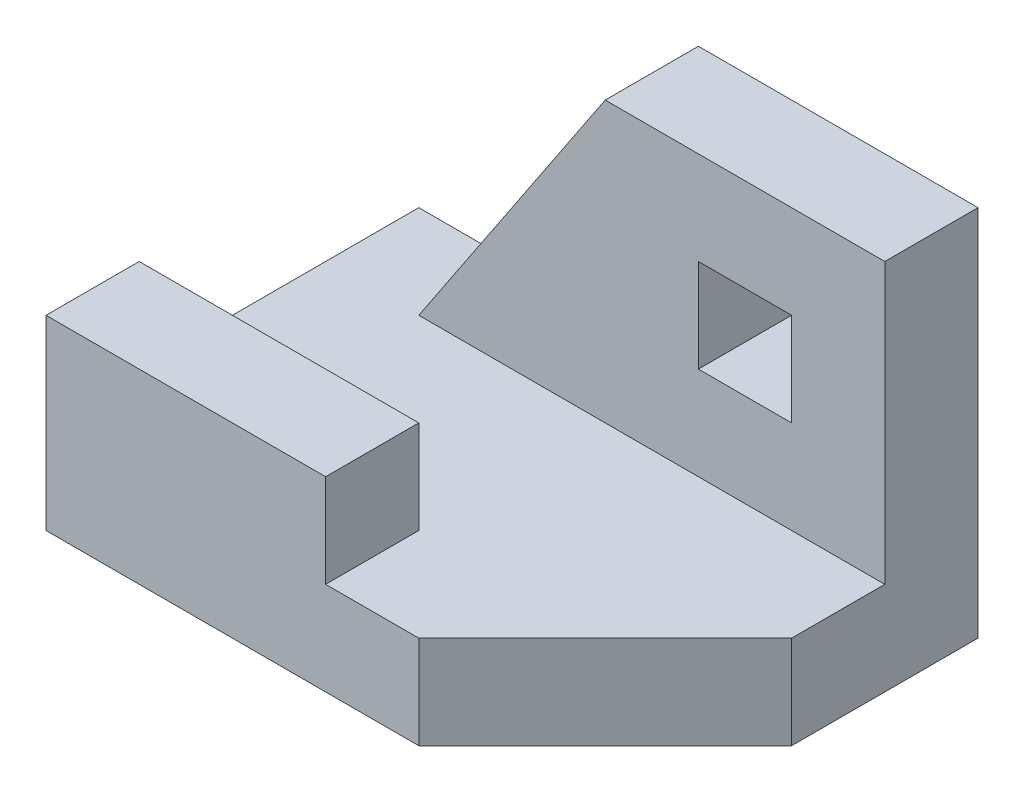
SolidWorks part; units mm, degrees
ref_plane "前基準面" through (0, 0, 0) normal (0, 0, 1) x (1, 0, 0)
ref_plane "上基準面" through (0, 0, 0) normal (0, 1, 0) x (1, 0, 0)
ref_plane "右基準面" through (0, 0, 0) normal (1, 0, 0) x (0, 0, -1)
sketch "草圖1" plane through (0, 0, 0) normal (0, 1, 0) x (1, 0, 0)
  line L0 (4, 0) -> (6, 2)
  line L1 (0, 0) -> (4, 0)
  line L2 (0, 0) -> (0, 4)
  line L3 (0, 4) -> (6, 4)
  line L4 (6, 2) -> (6, 4)
  line L5 (0, 1) -> (3, 1)
  line L6 (3, 1) -> (3, 0)
  line L7 (1, 4) -> (1, 3)
  line L8 (1, 3) -> (6, 3)
  dimension "D1" = 6
  dimension "D2" = 4
  dimension "D3" = 2
  dimension "D4" = 4
  dimension "D5" = 3
  dimension "D6" = 1
  dimension "D7" = 1
  dimension "D8" = 1
extrude "填料-伸長1" add sketch "草圖1" along normal blind 1 contours L7 L8 L4 L3 | L8 L7 L3 L2 L5 L6 L1 L0 L4 | L6 L5 L2 L1 region at (2.8095, 0, -1.9762) region at (1.5, 0, -0.5) region at (3.5, 0, -3.5)
extrude "填料-伸長2" add sketch "草圖1<3>" along normal blind 2 contours L6 L5 L2 L1 region at (1.5, 0, -0.5)
sketch "草圖1<3>" plane through (0, 0, 0) normal (0, 1, 0) x (1, 0, 0) same geometry as "草圖1"
extrude "填料-伸長3" add sketch "草圖1<4>" along normal blind 4 contours L7 L8 L4 L3 region at (3.5, 0, -3.5)
sketch "草圖1<4>" plane through (0, 0, 0) normal (0, 1, 0) x (1, 0, 0) same geometry as "草圖1"
sketch "草圖2" plane through (0, 0, -3) normal (0, 0, 1) x (1, 0, 0)
  line L0 (1, 4) -> (6, 4) construction
  line L1 (4, 2) -> (5, 2)
  line L2 (4, 2) -> (4, 3)
  line L3 (4, 3) -> (5, 3)
  line L4 (5, 2) -> (5, 3)
  line L5 (4, 2) -> (5, 3) construction
  line L6 (4, 3) -> (5, 2) construction
  line L7 (6, 4) -> (6, 1) construction
  line L8 (1, 4) -> (3, 4)
  line L9 (3, 4) -> (1, 1)
  line L10 (1, 1) -> (1, 4)
  point P0 (4.5, 2.5)
  dimension "D1" = 1
  dimension "D2" = 1
  dimension "D3" = 1
  dimension "D4" = 1
  dimension "D5" = 2
extrude "除料-伸長1" cut sketch "草圖2" against normal blind 4
